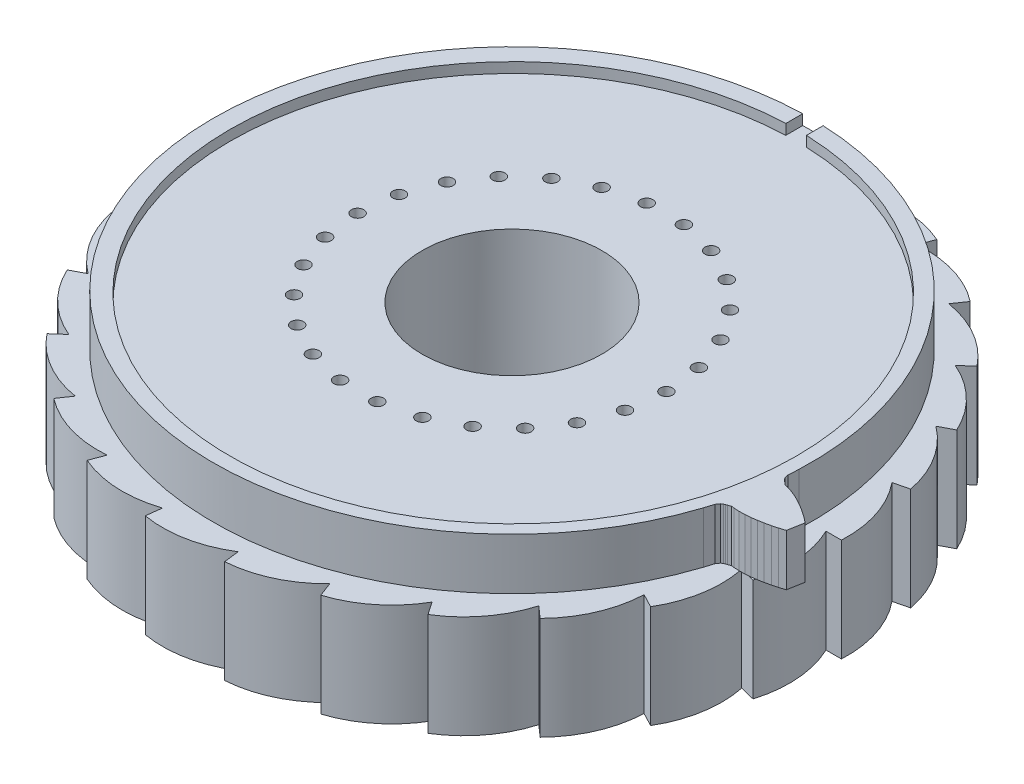
SolidWorks part; units mm, degrees
material "1060 Alloy"
ref_plane "Front Plane" through (0, 0, 0) normal (0, 0, 1) x (1, 0, 0)
ref_plane "Top Plane" through (0, 0, 0) normal (0, 1, 0) x (1, 0, 0)
ref_plane "Right Plane" through (0, 0, 0) normal (1, 0, 0) x (0, 0, -1)
sketch "Sketch1" plane through (0, 0, 0) normal (0, 1, 0) x (1, 0, 0)
  line L0 (0, 0) -> (54.8903, 0) construction
  line L1 (0, 0) -> (47.5263, 11.7142) construction
  line L2 (0, 0) -> (29.6137, 7.2991)
  line L3 (0, 0) -> (32, 0)
  circle A0 centre (0, 0) radius 32 construction
  circle A1 centre (0, 0) radius 30.5 construction
  arc A2 (29.6137, 7.2991) -> (32, 0) centre (21.3514, 0.5583) cw
  circle A3 centre (0, 0) radius 31.25 construction
  dimension "D1" = 62.5
  dimension "D2" = 1.5
  dimension "D4" = 0.75
  dimension "D3" = 13.846
extrude "Extrude ratchet edge" add sketch "Sketch1" along normal blind 10
pattern_circular "Pattern edge to form gear" count 26 over 360 about axis through (0, 10, 0) along (0, -1, 0) of "Extrude ratchet edge" reverse direction yes
sketch "Sketch12" plane through (0, 10, 0) normal (0, 1, 0) x (1, 0, 0)
  line L0 (28.9274, -2.1257) -> (29.0264, -2.5152)
  line L1 (29.0264, -2.5152) -> (29.1427, -2.6718)
  line L2 (29.1427, -2.6718) -> (29.2623, -2.7873)
  line L3 (29.2623, -2.7873) -> (29.3837, -2.8801)
  line L4 (29.3837, -2.8801) -> (29.6242, -3.0821)
  line L5 (29.6242, -3.0821) -> (29.8792, -3.1399)
  line L6 (29.8792, -3.1399) -> (30.3843, -3.2992)
  line L7 (30.3843, -3.2992) -> (30.8844, -3.4996)
  line L8 (30.8844, -3.4996) -> (31.3799, -3.7334)
  line L9 (31.3799, -3.7334) -> (31.8708, -3.9966)
  line L10 (31.8708, -3.9966) -> (32.3568, -4.2867)
  line L11 (32.3568, -4.2867) -> (32.8378, -4.602)
  line L12 (32.8378, -4.602) -> (33.3134, -4.9413)
  line L13 (33.3134, -4.9413) -> (33.7833, -5.3035)
  line L14 (33.7833, -5.3035) -> (33.502, -6.8593)
  line L15 (33.502, -6.8593) -> (32.9351, -7.0341)
  line L16 (32.9351, -7.0341) -> (32.3708, -7.1854)
  line L17 (32.3708, -7.1854) -> (31.8099, -7.3124)
  line L18 (31.8099, -7.3124) -> (31.253, -7.414)
  line L19 (31.253, -7.414) -> (30.7011, -7.4887)
  line L20 (30.7011, -7.4887) -> (30.1551, -7.5342)
  line L21 (30.1551, -7.5342) -> (29.6165, -7.5468)
  line L22 (29.6165, -7.5468) -> (29.0876, -7.5192)
  line L23 (29.0876, -7.5192) -> (28.8285, -7.4842)
  line L24 (28.8285, -7.4842) -> (28.5325, -7.5891)
  line L25 (28.5325, -7.5891) -> (28.3863, -7.6336)
  line L26 (28.3863, -7.6336) -> (28.2339, -7.6999)
  line L27 (28.2339, -7.6999) -> (28.07, -7.8059)
  line L28 (28.07, -7.8059) -> (27.841, -8.136)
  line L29 (27.841, -8.136) -> (27.578, -8.987)
  line L779 (28.9844, -1.1053) -> (28.9274, -2.1257)
  arc A0 (27.578, -8.987) -> (28.9844, -1.1053) centre (0, 0) cw
extrude "Gear face" add sketch "Sketch12" along normal blind 5
sketch "Sketch7" plane through (0, 15, 0) normal (0, 1, 0) x (1, 0, 0)
  circle A0 centre (0, 0) radius 8.7313
  dimension "D1" = 17.4625
sketch "Sketch10" plane through (0, 15, 0) normal (0, 1, 0) x (1, 0, 0)
  line L0 (-0.7538, 29.3517) -> (-0.7538, 27.3517)
  line L1 (1.2462, 27.3517) -> (1.2462, 29.3517)
  line L2 (1.2462, 29.3517) -> (-0.7538, 29.3517)
  line L3 (0.2462, -0.1301) -> (0.2462, 41.1735) construction
  line L4 (0.2462, -0.1301) -> (0.2462, 36.6199) construction
  arc A0 (-0.7538, 27.3517) -> (1.2462, 27.3517) centre (0.2462, -0.1301) ccw
  dimension "D1" = 2
extrude "PCB inset" cut sketch "Sketch10" against normal blind 1
extrude "Cut bearing hole" cut sketch "Sketch7" against normal through all
sketch "Sketch11" plane through (0, 0, 0) normal (0, -1, 0) x (1, 0, 0)
  line L0 (1, -29.4818) -> (1, -27.4818)
  line L1 (-1, -27.4818) -> (-1, -29.4818)
  line L2 (-1, -29.4818) -> (1, -29.4818)
  line L3 (0, 0) -> (0, -100.666) construction
  arc A0 (1, -27.4818) -> (-1, -27.4818) centre (0, 0) ccw
  point P0 (0, -29.4818)
  dimension "D2" = 2
  dimension "D3" = 27.5
  dimension "D1" = 2
  dimension "D4" = 2
extrude "PCB inset rear" cut sketch "Sketch11" against normal blind 1
sketch "pin holes" plane through (0, 14, 0) normal (0, 1, 0) x (1, 0, 0)
  circle A0 centre (15, 0) radius 0.6
  circle A1 centre (14.5641, -3.5897) radius 0.6
  circle A2 centre (13.2818, -6.9708) radius 0.6
  circle A3 centre (11.2277, -9.9468) radius 0.6
  circle A4 centre (8.521, -12.3448) radius 0.6
  circle A5 centre (5.3191, -14.0252) radius 0.6
  circle A6 centre (1.8081, -14.8906) radius 0.6
  circle A7 centre (-1.8081, -14.8906) radius 0.6
  circle A8 centre (-5.3191, -14.0252) radius 0.6
  circle A9 centre (-8.521, -12.3448) radius 0.6
  circle A10 centre (-11.2277, -9.9468) radius 0.6
  circle A11 centre (-13.2818, -6.9708) radius 0.6
  circle A12 centre (-14.5641, -3.5897) radius 0.6
  circle A13 centre (-15, 0) radius 0.6
  circle A14 centre (-14.5641, 3.5897) radius 0.6
  circle A15 centre (-13.2818, 6.9708) radius 0.6
  circle A16 centre (-11.2277, 9.9468) radius 0.6
  circle A17 centre (-8.521, 12.3448) radius 0.6
  circle A18 centre (-5.3191, 14.0252) radius 0.6
  circle A19 centre (-1.8081, 14.8906) radius 0.6
  circle A20 centre (1.8081, 14.8906) radius 0.6
  circle A21 centre (5.3191, 14.0252) radius 0.6
  circle A22 centre (8.521, 12.3448) radius 0.6
  circle A23 centre (11.2277, 9.9468) radius 0.6
  circle A24 centre (13.2818, 6.9708) radius 0.6
  circle A25 centre (14.5641, 3.5897) radius 0.6
  point P55 (0, 0)
  dimension "D1" = 1.2
  dimension "D2" = 15
  dimension "D3" = 26
extrude "Pin holes cut" cut sketch "pin holes" against normal through all
sketch "Sketch14" [suppressed] plane through (0, 14, 0) normal (0, 1, 0) x (1, 0, 0)
  line L0 (0, 0) -> (0, 34.7764) construction
  circle A0 centre (0, 25) radius 1.5875
  circle A1 centre (21.6506, -12.5) radius 1.5875
  circle A2 centre (-21.6506, -12.5) radius 1.5875
  point P11 (0, 0)
  dimension "D1" = 3.175
  dimension "D2" = 25
  dimension "D3" = 3
extrude "Cut-Extrude2" [suppressed] cut sketch "Sketch14" against normal through all
sketch "Sketch13" [suppressed] plane through (0, 10, 0) normal (0, 1, 0) x (1, 0, 0)
  circle A0 centre (0, 0) radius 52.9385
extrude "Cut in half for 3D print" [suppressed] cut sketch "Sketch13" along normal through all
equation "\"Bearing size\"= 17.4625mm"
equation "\"D1@Sketch7\" = \"Bearing size\""
equation "\"dedendum\"= 2mm"
equation "\"addendum\"= 2mm"
equation "\"D5@Iteration wheel\" = \"addendum\""
equation "\"base diameter\"=58"
equation "\"alpha\"= sqr ( ( \"base diameter\" + \"dedendum\" ) ^ 2 - \"base diameter\" ^ 2 ) / \"base diameter\" * 180 / PI - \"phi\""
equation "\"phi\"= 20"
